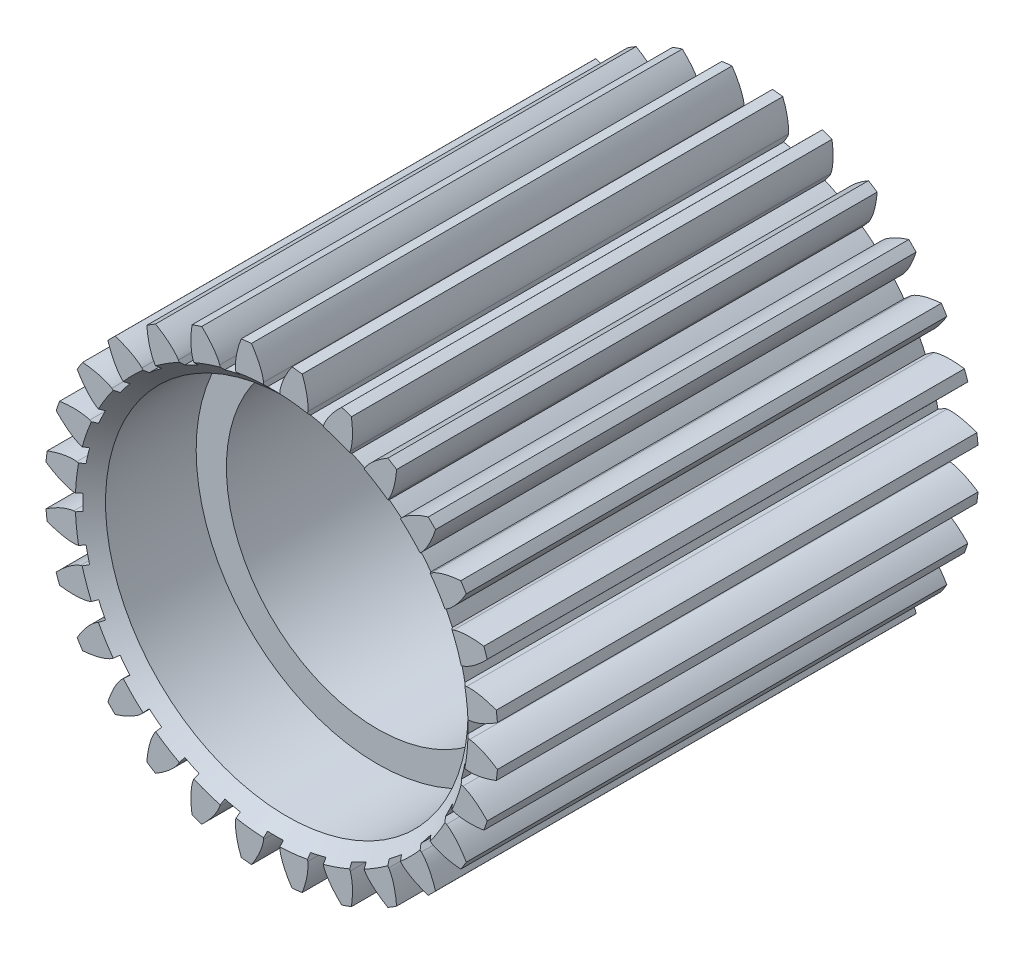
SolidWorks part; units mm, degrees
material "PLA"
ref_plane "Front Plane" through (0, 0, 0) normal (0, 0, 1) x (1, 0, 0)
ref_plane "Top Plane" through (0, 0, 0) normal (0, 1, 0) x (1, 0, 0)
ref_plane "Right Plane" through (0, 0, 0) normal (1, 0, 0) x (0, 0, -1)
sketch "Sketch1" plane through (0, 0, 0) normal (0, 0, 1) x (1, 0, 0)
  circle A0 centre (0, 0) radius 12.5
  dimension "D1" = 25
extrude "Boss-Extrude1" add sketch "Sketch1" along normal mid plane 8.418
sketch "Sketch2" plane through (0, 0, 0) normal (0, 0, 1) x (1, 0, 0)
  line L0 (0, 0) -> (11.9981, 0.2138) construction
  line L1 (0, 0) -> (12, 0) construction
  line L2 (0, 0) -> (11.9981, -0.2138) construction
  line L3 (11.2721, -0.2009) -> (11.3732, -0.2027)
  line L4 (11.2745, 0.2009) -> (11.3732, 0.2027)
  circle A0 centre (0, 0) radius 12 construction
  circle A1 centre (0, 0) radius 11.2763 construction
  circle A2 centre (0, 0) radius 11.375
  circle A3 centre (0, 0) radius 12.5 construction
  circle A4 centre (0, 0) radius 12.5
  spline S0 degree 4 poles (11.2745, 0.2009) (11.2784, 0.2011) (11.2892, 0.2016) (11.3096, 0.2032) (11.3428, 0.2069) (11.385, 0.213) (11.4394, 0.2225) (11.5033, 0.2357) (11.5732, 0.2525) (11.6488, 0.273) (11.724, 0.2956) (11.7986, 0.32) (11.8726, 0.346) (11.9619, 0.3795) (12.0682, 0.4225) (12.1915, 0.4768) (12.3302, 0.5432) (12.47, 0.6159) (12.6064, 0.6915) (12.7427, 0.7727) (12.8735, 0.8545) (13.0077, 0.9443) (13.1307, 1.0295) (13.2665, 1.1303) (13.3755, 1.213) (13.5171, 1.3277) (13.6, 1.3971) (13.6963, 1.4801) (13.7386, 1.5179) (13.7646, 1.5412) knots 0 0 0 0 0 0.005377 0.015084 0.028532 0.04661 0.064855 0.092111 0.119476 0.146842 0.174209 0.201575 0.228941 0.256307 0.307035 0.361767 0.4165 0.471232 0.525964 0.580697 0.635429 0.690161 0.744894 0.799626 0.854358 0.909091 0.954545 1 1 1 1 1 construction
  spline S1 degree 4 poles (11.2745, 0.2009) (11.2784, 0.2011) (11.2892, 0.2016) (11.3096, 0.2032) (11.3428, 0.2069) (11.385, 0.213) (11.4394, 0.2225) (11.5033, 0.2357) (11.5732, 0.2525) (11.6488, 0.273) (11.724, 0.2956) (11.7986, 0.32) (11.8726, 0.346) (11.9619, 0.3795) (12.0682, 0.4225) (12.1915, 0.4768) (12.3302, 0.5432) (12.47, 0.6159) (12.6064, 0.6915) (12.7427, 0.7727) (12.8735, 0.8545) (13.0077, 0.9443) (13.1307, 1.0295) (13.2665, 1.1303) (13.3755, 1.213) (13.4864, 1.3028) (13.5401, 1.3472) (13.5674, 1.3701) knots 0 0 0 0 0 0.005377 0.015084 0.028532 0.04661 0.064855 0.092111 0.119476 0.146842 0.174209 0.201575 0.228941 0.256307 0.307035 0.361767 0.4165 0.471232 0.525964 0.580697 0.635429 0.690161 0.744894 0.799626 0.854358 0.909091 0.909091 0.909091 0.909091 0.909091
  spline S2 degree 4 poles (11.2721, -0.2009) (11.2759, -0.201) (11.2867, -0.2015) (11.3071, -0.2032) (11.3403, -0.2069) (11.3825, -0.213) (11.437, -0.2224) (11.5008, -0.2357) (11.5707, -0.2524) (11.6464, -0.273) (11.7216, -0.2955) (11.7962, -0.3199) (11.8702, -0.3459) (11.9594, -0.3795) (12.0658, -0.4225) (12.1891, -0.4768) (12.3277, -0.5432) (12.4676, -0.6158) (12.604, -0.6915) (12.7403, -0.7726) (12.8711, -0.8545) (13.0052, -0.9442) (13.1282, -1.0295) (13.264, -1.1302) (13.373, -1.213) (13.5146, -1.3277) (13.5975, -1.397) (13.6938, -1.48) (13.7361, -1.5179) (13.7622, -1.5412) knots 0 0 0 0 0 0.005377 0.015084 0.028532 0.04661 0.064855 0.092111 0.119476 0.146842 0.174209 0.201575 0.228941 0.256307 0.307035 0.361767 0.4165 0.471232 0.525964 0.580697 0.635429 0.690161 0.744894 0.799626 0.854358 0.909091 0.954545 1 1 1 1 1 construction
  spline S3 degree 4 poles (11.2721, -0.2009) (11.2759, -0.201) (11.2867, -0.2015) (11.3071, -0.2032) (11.3403, -0.2069) (11.3825, -0.213) (11.437, -0.2224) (11.5008, -0.2357) (11.5707, -0.2524) (11.6464, -0.273) (11.7216, -0.2955) (11.7962, -0.3199) (11.8702, -0.3459) (11.9594, -0.3795) (12.0658, -0.4225) (12.1891, -0.4768) (12.3277, -0.5432) (12.4676, -0.6158) (12.604, -0.6915) (12.7403, -0.7726) (12.8711, -0.8545) (13.0052, -0.9442) (13.1282, -1.0295) (13.264, -1.1302) (13.373, -1.213) (13.4839, -1.3028) (13.5376, -1.3471) (13.565, -1.3701) knots 0 0 0 0 0 0.005377 0.015084 0.028532 0.04661 0.064855 0.092111 0.119476 0.146842 0.174209 0.201575 0.228941 0.256307 0.307035 0.361767 0.4165 0.471232 0.525964 0.580697 0.635429 0.690161 0.744894 0.799626 0.854358 0.909091 0.909091 0.909091 0.909091 0.909091
  dimension "D1" = 24
  dimension "D2" = 22.5526
  dimension "D3" = 22.75
  dimension "D4" = 1.021
  dimension "D5" = 1.021
extrude "Cut-Extrude1" cut sketch "Sketch2" against normal through all both and the other way through all contours A2 A4 region at (12.0369, -0.0005, 0)
pattern_circular "CirPattern2" count 48 over 360 about axis through (0, 0, 4.209) along (0, 0, -1) of "Cut-Extrude1"
sketch "Sketch3" plane through (0, 0, 4.209) normal (0, 0, 1) x (1, 0, 0)
  circle A0 centre (0, 0) radius 5
  dimension "D1" = 10
sketch "Sketch4" plane through (0, 0, -4.209) normal (0, 0, -1) x (-1, 0, 0)
  circle A0 centre (0, 0) radius 7.5
  dimension "D1" = 15
extrude "Boss-Extrude2" add sketch "Sketch4" along normal blind 15.9054
sketch "Sketch5" plane through (0, 0, -20.1144) normal (0, 0, -1) x (-1, 0, 0)
  line L0 (0, 0) -> (7.5, 0) construction
  line L1 (0, 0) -> (7.4936, 0.3089) construction
  line L2 (0, 0) -> (7.4936, -0.3089) construction
  line L3 (6.5519, 0.2701) -> (6.3696, 0.2625)
  line L4 (6.5519, -0.2701) -> (6.3696, -0.2625)
  circle A0 centre (0, 0) radius 6.5778 construction
  circle A1 centre (0, 0) radius 6.375
  arc A2 (7.47, -0.67) -> (7.47, 0.67) centre (0, 0) ccw
  spline S0 degree 4 poles (6.5519, 0.2701) (6.5542, 0.2702) (6.5605, 0.2706) (6.5799, 0.2727) (6.618, 0.2785) (6.6647, 0.2883) (6.7181, 0.302) (6.7693, 0.3172) (6.8128, 0.3314) (6.856, 0.3466) (6.8988, 0.3628) (6.9503, 0.3836) (7.0118, 0.4101) (7.083, 0.4435) (7.1629, 0.4841) (7.2435, 0.5284) (7.322, 0.5743) (7.4004, 0.6235) (7.4755, 0.673) (7.5525, 0.7272) (7.6231, 0.7786) (7.7009, 0.8392) (7.7634, 0.8889) (7.8444, 0.9577) (7.8918, 0.9993) (7.9468, 1.049) (7.971, 1.0717) (7.9858, 1.0856) knots 0 0 0 0 0 0.005377 0.015084 0.04661 0.092111 0.119476 0.146842 0.174209 0.201575 0.228941 0.256307 0.307035 0.361767 0.4165 0.471232 0.525964 0.580697 0.635429 0.690161 0.744894 0.799626 0.854358 0.909091 0.954545 1 1 1 1 1 construction
  spline S1 degree 4 poles (6.5519, 0.2701) (6.5542, 0.2702) (6.5605, 0.2706) (6.5799, 0.2727) (6.618, 0.2785) (6.6647, 0.2883) (6.7181, 0.302) (6.7693, 0.3172) (6.8128, 0.3314) (6.856, 0.3466) (6.8988, 0.3628) (6.9503, 0.3836) (7.0118, 0.4101) (7.083, 0.4435) (7.1629, 0.4841) (7.2435, 0.5284) (7.322, 0.5743) (7.4004, 0.6235) (7.4755, 0.673) (7.5525, 0.7272) (7.6231, 0.7786) (7.7009, 0.8392) (7.7634, 0.8889) (7.8268, 0.9428) (7.8575, 0.9694) (7.8732, 0.9832) knots 0 0 0 0 0 0.005377 0.015084 0.04661 0.092111 0.119476 0.146842 0.174209 0.201575 0.228941 0.256307 0.307035 0.361767 0.4165 0.471232 0.525964 0.580697 0.635429 0.690161 0.744894 0.799626 0.854358 0.909091 0.909091 0.909091 0.909091 0.909091
  spline S2 degree 4 poles (6.5519, -0.2701) (6.5542, -0.2702) (6.5605, -0.2706) (6.5799, -0.2727) (6.618, -0.2785) (6.6647, -0.2883) (6.7181, -0.302) (6.7693, -0.3172) (6.8128, -0.3314) (6.856, -0.3466) (6.8988, -0.3628) (6.9503, -0.3836) (7.0118, -0.4101) (7.083, -0.4435) (7.1629, -0.4841) (7.2435, -0.5284) (7.322, -0.5743) (7.4004, -0.6235) (7.4755, -0.673) (7.5525, -0.7272) (7.6231, -0.7786) (7.7009, -0.8392) (7.7634, -0.8889) (7.8444, -0.9577) (7.8918, -0.9993) (7.9468, -1.049) (7.971, -1.0717) (7.9858, -1.0856) knots 0 0 0 0 0 0.005377 0.015084 0.04661 0.092111 0.119476 0.146842 0.174209 0.201575 0.228941 0.256307 0.307035 0.361767 0.4165 0.471232 0.525964 0.580697 0.635429 0.690161 0.744894 0.799626 0.854358 0.909091 0.954545 1 1 1 1 1 construction
  spline S3 degree 4 poles (6.5519, -0.2701) (6.5542, -0.2702) (6.5605, -0.2706) (6.5799, -0.2727) (6.618, -0.2785) (6.6647, -0.2883) (6.7181, -0.302) (6.7693, -0.3172) (6.8128, -0.3314) (6.856, -0.3466) (6.8988, -0.3628) (6.9503, -0.3836) (7.0118, -0.4101) (7.083, -0.4435) (7.1629, -0.4841) (7.2435, -0.5284) (7.322, -0.5743) (7.4004, -0.6235) (7.4755, -0.673) (7.5525, -0.7272) (7.6231, -0.7786) (7.7009, -0.8392) (7.7634, -0.8889) (7.8268, -0.9428) (7.8575, -0.9694) (7.8732, -0.9832) knots 0 0 0 0 0 0.005377 0.015084 0.04661 0.092111 0.119476 0.146842 0.174209 0.201575 0.228941 0.256307 0.307035 0.361767 0.4165 0.471232 0.525964 0.580697 0.635429 0.690161 0.744894 0.799626 0.854358 0.909091 0.909091 0.909091 0.909091 0.909091
  dimension "D2" = 12.75
  dimension "D3" = 15
  dimension "D1" = 13.1557
  dimension "D4" = 2.36
  dimension "D5" = 2.36
extrude "Cut-Extrude2" cut sketch "Sketch5" against normal up to surface (15.9054 mm away) contours A2 A1 region at (-7.0303, 0, -20.1144) up to face at (7.5, 0, -4.209)
pattern_circular "CirPattern3" count 28 over 360 about axis through (0, 0, -20.1144) along (0, 0, 1) of "Cut-Extrude2"
extrude "Cut-Extrude3" cut sketch "Sketch3" against normal through all contours A0
sketch "Sketch7" plane through (0, 0, -20.1144) normal (0, 0, -1) x (-1, 0, 0)
  circle A0 centre (0, 0) radius 6
  dimension "D1" = 12
extrude "Cut-Extrude4" cut sketch "Sketch7" against normal blind 3.5
ref_plane "Plane1" through (0, 0, -7.9527) normal (0, 0, -1) x (-1, 0, 0)
mirror "Mirror1" [suppressed] about plane through (0, 0, -7.9527) normal (0, 0, -1)
sketch "Sketch8" plane through (0, 0, 4.209) normal (0, 0, 1) x (1, 0, 0)
  circle A0 centre (0, 0) radius 16.2595
extrude "Cut-Extrude5" cut sketch "Sketch8" against normal up to surface (8.418 mm away) up to face at (0, 0, -4.209)
ref_plane "Plane2" through (0, 0, -12.1617) normal (0, 0, -1) x (-1, 0, 0)
mirror "Mirror3" about plane through (0, 0, -12.1617) normal (0, 0, -1) of "Cut-Extrude4"
chamfer "Chamfer1" distance 0.5 angle 45 2 edges at (-6, 0, -20.1144) (-6, 0, -4.209)
equation "\"module\" = 0.5"
equation "\"pressure angle\" = 20.0"
equation "\"h_a\" = 0.5"
equation "\"h_b\" = 0.625"
equation "\"clr_tip_root\" = 0.125"
equation "\"D1@Sketch1\" = \"dp_p_b\" + 2 * \"h_a\""
equation "\"D1@Boss-Extrude1\"=\"fw_p_b\" -  \"standard_clearance_1_5mm\""
equation "\"D1@Sketch2\" = \"dp_p_b\""
equation "\"D2@Sketch2\"= \"db_p_b\""
equation "\"D3@Sketch2\" = \"dp_p_b\" - 2 * \"h_b\""
equation "\"Nr_s\" = 132"
equation "\"pressure_angle\" = 20.0"
equation "\"h_f\" = 0.625"
equation "\"dp_r_s\" = 66.0"
equation "\"bearing_ID\" = 60"
equation "\"bearing_OD\" = 78"
equation "\"bearing_height\" = 10"
equation "\"clearance_planet\" = 1.5"
equation "\"case_dist\" = 6.5"
equation "\"Motor_case_OD_max\" = 111.3"
equation "\"case_mounting_PCD\" = 103.8"
equation "\"bearing mount thickness\" = 8"
equation "\"case_mounting_hole_dia\" = 3"
equation "\"output_mounting_PCD\" = 86"
equation "\"output_mounting_hole_dia\" = 4"
equation "\"clearance_case_mount_holes_shell_thickness\" = 1"
equation "\"motor_case_OD_base\" = 101.8"
equation "\"sec_carrier_thickness\" = 5"
equation "\"sun_coupler_hub_thickness\" = 4"
equation "\"clearance_sun_coupler_sec_carrier\" = 1.5"
equation "\"clearance_motor_and_case\" = 5"
equation "\"motor_OD\" = 86.8"
equation "\"Motor_case_thickness\" = 2.5"
equation "\"Motor_case_ID\" = 96.8"
equation "\"case_mounting_hole_shift\" = 1.0"
equation "\"output_mounting_nut_wrench_size\" = 7"
equation "\"output_mounting_nut_thickness\" = 3.2"
equation "\"case_mounting_hole_allen_socket_dia\" = 5.5"
equation "\"output_mounting_nut_depth\" = 3"
equation "\"case_mounting_bolt_depth\" = 4.5"
equation "\"Ns\" = 56"
equation "\"ring_radial_thickness\" = 5"
equation "\"ring_to_chamfer_clearance\" = 1.5"
equation "\"Motor_case_OD_base_to_chamfer\" = 5"
equation "\"pattern_offset_from_motor_case_OD_base\" = 3"
equation "\"pattern_bulge_dia\" = 3"
equation "\"pattern_num_bulge\" = 18"
equation "\"pattern_depth\" = 2"
equation "\"motor_height\" = 26.5"
equation "\"case_mounting_wrench_size\" = 5.5"
equation "\"case_mounting_nut_clearance\" = 2"
equation "\"base_plate_thickness\" = 4"
equation "\"case_mounting_nut_thickness\" = 2.4"
equation "\"case_mounting_surface_height\" = 4"
equation "\"motor_mount_hole_PCD\" = 32"
equation "\"motor_mount_hole_dia\" = 4"
equation "\"motor_mount_hole_num\" = 4"
equation "\"central_hole_offset_from_motor_mount_PCD\" = 5"
equation "\"wire_slot_dist_from_center\" = 38"
equation "\"wire_slot_length\" = 10"
equation "\"wire_slot_radius\" = 2.5"
equation "\"driver_upper_holes_dist_from_center\" = 29"
equation "\"driver_lower_holes_dist_from_center\" = 13"
equation "\"driver_side_holes_dist_from_center\" = 22.5"
equation "\"driver_mount_holes_dia\" = 3"
equation "\"driver_mount_inserts_OD\" = 4.8"
equation "\"driver_mount_thickness\" = 1.5"
equation "\"driver_mount_height\" = 6"
equation "\"air_flow_hole_offset\" = 3"
equation "\"num_planet\" = 4"
equation "\"planet_pin_bolt_dia\" = 5"
equation "\"planet_pin_socket_head_dia\" = 8.5"
equation "\"carrier_PCD\" = 52.0"
equation "\"planet_shaft_dia\" = 8"
equation "\"planet_shaft_step_offset\" = 1"
equation "\"carrier_trapezoidal_support_sun_offset\" = 5"
equation "\"carrier_trapezoidal_support_hole_PCD_offset_bearing_ID\" = 4"
equation "\"carrier_trapezoidal_support_hole_dia\" = 3"
equation "\"carrier_trapezoidal_support_hole_socket_head_dia\" = 5.5"
equation "\"carrier_bearing_step_width\" = 1.5"
equation "\"standard_clearance_1_5mm\" = 1.5"
equation "\"standard_fillet_1_5mm\" = 1.5"
equation "\"sun_shaft_bearing_OD\" = 16"
equation "\"sun_shaft_bearing_width\" = 5"
equation "\"standard_bearing_insertion_chamfer\" = 0.5"
equation "\"carrier_trapezoidal_support_hole_wrench_size\" = 5.5"
equation "\"planet_pin_bolt_wrench_size\" = 8"
equation "\"planet_bearing_OD\" = 12"
equation "\"planet_bearing_width\" = 3.5"
equation "\"planet_bore\" = 10"
equation "\"D1@Sketch3\"=\"planet_bore\""
equation "\"Np_b\" = 48"
equation "\"dp_s\" = 28.0"
equation "\"db_s\" = 26.311393382005434"
equation "\"fw_s_calc\" = 2.7970255760332914"
equation "\"alpha_s\" = 0.8539582918412485"
equation "\"beta_s\" = 1.5063691306032174"
equation "\"dp_p_b\" = 24.0"
equation "\"db_p_b\" = 22.552622898861802"
equation "\"fw_p_s\" = 15.90536252346366"
equation "\"alpha_p_b\" = 0.8539582918412414"
equation "\"beta_p_b\" = 2.042083416317517"
equation "\"motor_output_hole_PCD\" = 23"
equation "\"motor_output_hole_dia\" = 4"
equation "\"motor_output_hole_num\" = 4"
equation "\"sun_shaft_bearing_ID\" = 8"
equation "\"sun_hub_dia\" = 30.0"
equation "\"sun_central_bolt_dia\" = 5"
equation "\"sun_central_bolt_socket_head_dia\" = 8.5"
equation "\"fw_s_used\" = 33.32338113475014"
equation "\"motor_output_hole_CSK_OD\" = 8"
equation "\"motor_output_hole_CSK_head_height\" = 2.0"
equation "\"bearing_retainer_thickness\" = 2"
equation "\"Np_s\" = 28"
equation "\"fw_p_b\" = 9.918018611286483"
equation "\"dp_p_s\" = 14.0"
equation "\"db_p_s\" = 13.155696691002717"
equation "\"alpha_p_s\" = 0.8539582918412485"
equation "\"beta_p_s\" = 4.720654844888932"
equation "\"D1@Sketch4\"=\"dp_p_s\" + 2 * \"h_a\""
equation "\"D1@Boss-Extrude2\"=\"fw_p_s\""
equation "\"D2@Sketch5\"=\"dp_p_s\" - 2 * \"h_b\""
equation "\"D3@Sketch5\"=\"dp_p_s\"+2 * \"h_a\" "
equation "\"D1@Sketch5\"=\"db_p_s\""
equation "\"D1@CirPattern3\"=\"Np_s\""
equation "\"D4@Sketch5\"=\"beta_p_s\"/2"
equation "\"D5@Sketch5\"=\"beta_p_s\"/2"
equation "\"D4@Sketch2\"=\"beta_p_b\"/2"
equation "\"D5@Sketch2\"=\"beta_p_b\"/2"
equation "\"D1@Sketch7\"=\"planet_bearing_OD\""
equation "\"D1@Cut-Extrude4\"=\"planet_bearing_width\""
equation "\"D1@Chamfer1\"=\"standard_bearing_insertion_chamfer\""
equation "\"D1@CirPattern2\"=\"Np_b\""
equation "\"Nr_b\" = 152"
equation "\"dp_r_b\" = 76.0"
equation "\"db_r_b\" = 71.41663917972905"
equation "\"fw_r_b\" = 9.918018611286483"
equation "\"alpha_r_b\" = 0.8539582918412236"
equation "\"beta_r_b\" = 2.8921271099982366"
equation "\"ring_OD_b\" = 86.0"
equation "\"Fillet10\"= IIF ( \"ring_OD_b\" > ( \"bearing_OD\" + 2 * \"bearing mount thickness\" ) , \"suppressed\" , \"unsuppressed\" )"
equation "\"Fillet11\"= IIF ( \"ring_OD_b\" < ( \"bearing_OD\" + 2 * \"bearing mount thickness\" ) , \"suppressed\" , \"unsuppressed\" )"
equation "\"clr_tip_root_s\" = 0.125"
equation "\"db_r_s\" = 62.01971297186996"
equation "\"fw_r_s\" = 14.40536252346366"
equation "\"alpha_r_s\" = 0.8539582918412449"
equation "\"beta_r_s\" = 3.071552947318853"
equation "\"small_ring_case_thickness\" = 4"
equation "\"carrier_thickness\" = 4"
equation "\"small_ring_output_wall_thickness\" = 5"
equation "\"small_ring_output_wall_to_bearing_shaft_attachement_hole_dia\" = 4"
equation "\"small_ring_output_wall_to_bearing_shaft_attachement_hole_depth\" = 6.5"
equation "\"small_ring_output_wall_to_bearing_shaft_attachement_nut_wrench\" = 7"
equation "\"small_ring_output_wall_to_bearing_shaft_attachement_nut_thickness\" = 3.2"
equation "\"small_ring_output_wall_to_bearing_shaft_attachement_hole_pcd\" = 12"
equation "\"small_ring_output_wall_to_bearing_shaft_attachement_hole_num\" = 3"
equation "\"small_ring_output_wall_to_bearing_shaft_attachement_hole_CSK_OD\" = 8"
equation "\"small_ring_output_wall_to_bearing_shaft_attachement_hole_CSK_head_height\" = 2.0"
equation "\"carrier_small_ring_inner_bearing_ID\" = 20"
equation "\"carrier_small_ring_inner_bearing_OD\" = 32"
equation "\"carrier_small_ring_inner_bearing_height\" = 7"
equation "\"carrier_small_ring_inner_bearing_flap\" = 2"
equation "\"gear_casing_big_ring_to_bearing_dist\" = 24.90536252346366"
equation "\"gear_casing_thickness\" = 4"
